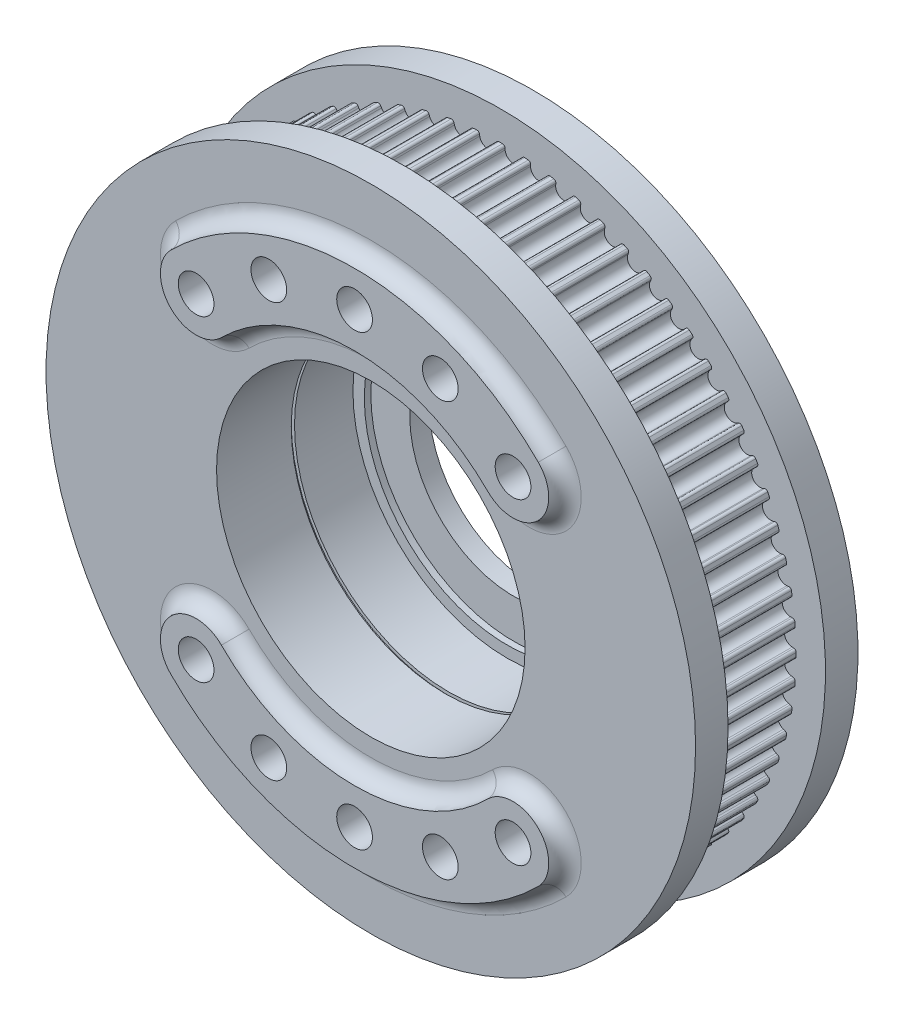
SolidWorks part; units mm, degrees
ref_plane "前视基准面" through (0, 0, 0) normal (0, 0, 1) x (1, 0, 0)
ref_plane "上视基准面" through (0, 0, 0) normal (0, 1, 0) x (1, 0, 0)
ref_plane "右视基准面" through (0, 0, 0) normal (1, 0, 0) x (0, 0, -1)
sketch "Sketch2" plane through (0, 0, 0) normal (0, 0, 1) x (1, 0, 0)
  circle A0 centre (0, 0) radius 90.99
  dimension "D1" = 181.98
extrude "Extrude1" add sketch "Sketch2" along normal mid plane 30
sketch "Sketch1" plane through (0, 0, 0) normal (0, 0, 1) x (1, 0, 0)
  line L0 (0, 0) -> (0, 91.675) construction
  line L1 (0, 0) -> (-3.9988, 91.5877) construction
  line L2 (-1.3223, 90.2696) -> (-1.3645, 89.7327)
  line L3 (-6.5503, 90.0413) -> (-6.4614, 89.5101)
  circle A0 centre (0, 0) radius 91.675 construction
  arc A1 (-0.5494, 90.9883) -> (-7.3828, 90.69) centre (0, 0) ccw
  arc A2 (-6.4614, 89.5101) -> (-1.3645, 89.7327) centre (-3.9266, 89.9343) ccw
  arc A3 (-0.5494, 90.9883) -> (-1.3223, 90.2696) centre (-0.5447, 90.2084) ccw
  arc A4 (-7.3828, 90.69) -> (-6.5503, 90.0413) centre (-7.3196, 89.9126) cw
  point P4 (91.5877, 3.9988)
  point P5 (90.8907, 11.966)
  point P6 (89.5019, 19.8421)
  point P7 (87.432, 27.5672)
  point P8 (84.6967, 35.0825)
  point P9 (81.3167, 42.3308)
  point P10 (77.3179, 49.2569)
  point P11 (72.7307, 55.8082)
  point P12 (67.5899, 61.9347)
  point P13 (61.9347, 67.5899)
  point P14 (55.8082, 72.7307)
  point P15 (49.2569, 77.3179)
  point P16 (42.3308, 81.3167)
  point P17 (35.0825, 84.6967)
  point P18 (27.5672, 87.432)
  point P19 (19.8421, 89.5019)
  point P20 (11.966, 90.8907)
  point P21 (3.9988, 91.5877)
  point P22 (-3.9988, 91.5877)
  point P23 (-11.966, 90.8907)
  point P24 (-19.8421, 89.5019)
  point P25 (-27.5672, 87.432)
  point P26 (-35.0825, 84.6967)
  point P27 (-42.3308, 81.3167)
  point P28 (-49.2569, 77.3179)
  point P29 (-55.8082, 72.7307)
  point P30 (-61.9347, 67.5899)
  point P31 (-67.5899, 61.9347)
  point P32 (-72.7307, 55.8082)
  point P33 (-77.3179, 49.2569)
  point P34 (-81.3167, 42.3308)
  point P35 (-84.6967, 35.0825)
  point P36 (-87.432, 27.5672)
  point P37 (-89.5019, 19.8421)
  point P38 (-90.8907, 11.966)
  point P39 (-91.5877, 3.9988)
  point P40 (-91.5877, -3.9988)
  point P41 (-90.8907, -11.966)
  point P42 (-89.5019, -19.8421)
  point P43 (-87.432, -27.5672)
  point P44 (-84.6967, -35.0825)
  point P45 (-81.3167, -42.3308)
  point P46 (-77.3179, -49.2569)
  point P47 (-72.7307, -55.8082)
  point P48 (-67.5899, -61.9347)
  point P49 (-61.9347, -67.5899)
  point P50 (-55.8082, -72.7307)
  point P51 (-49.2569, -77.3179)
  point P52 (-42.3308, -81.3167)
  point P53 (-35.0825, -84.6967)
  point P54 (-27.5672, -87.432)
  point P55 (-19.8421, -89.5019)
  point P56 (-11.966, -90.8907)
  point P57 (-3.9988, -91.5877)
  point P58 (3.9988, -91.5877)
  point P59 (11.966, -90.8907)
  point P60 (19.8421, -89.5019)
  point P61 (27.5672, -87.432)
  point P62 (35.0825, -84.6967)
  point P63 (42.3308, -81.3167)
  point P64 (49.2569, -77.3179)
  point P65 (55.8082, -72.7307)
  point P66 (61.9347, -67.5899)
  point P67 (67.5899, -61.9347)
  point P68 (72.7307, -55.8082)
  point P69 (77.3179, -49.2569)
  point P70 (81.3167, -42.3308)
  point P71 (84.6967, -35.0825)
  point P72 (87.432, -27.5672)
  point P73 (89.5019, -19.8421)
  point P74 (90.8907, -11.966)
  point P75 (91.5877, -3.9988)
  dimension "D1" = 183.35
  dimension "D2" = 181.98
  dimension "D3" = 5.14
  dimension "D4" = 3.54
  dimension "D5" = 1.56
  dimension "D6" = 7
extrude "Extrude2" cut sketch "Sketch1" along normal mid plane 30
pattern_circular "CirPattern1" count 72 over 360 about axis through (0, 0, 0) along (0, 0, 1) of "Extrude2"
sketch "Sketch3" plane through (0, 0, 15) normal (0, 0, 1) x (1, 0, 0)
  circle A0 centre (0, 0) radius 100
  dimension "D1" = 200
extrude "Extrude3" add sketch "Sketch3" along normal blind 10
sketch "Sketch4" plane through (0, 0, -15) normal (0, 0, -1) x (-1, 0, 0)
  circle A0 centre (0, 0) radius 100
  circle A1 centre (0, 0) radius 100 construction
extrude "Extrude4" add sketch "Sketch4" along normal blind 10
sketch "Sketch6" plane through (0, 0, -25) normal (0, 0, -1) x (-1, 0, 0)
  line L0 (0, 0) -> (0, 100) construction
  line L1 (-48.7904, 48.7904) -> (0, 0) construction
  line L2 (0, 0) -> (100, 0) construction
  arc A0 (48.7904, 48.7904) -> (-48.7904, 48.7904) centre (0, 0) ccw construction
  arc A1 (56.5685, 56.5685) -> (-56.5685, 56.5685) centre (0, 0) ccw
  arc A2 (41.0122, 41.0122) -> (-41.0122, 41.0122) centre (0, 0) ccw
  arc A3 (41.0122, 41.0122) -> (56.5685, 56.5685) centre (48.7904, 48.7904) ccw
  arc A4 (-56.5685, 56.5685) -> (-41.0122, 41.0122) centre (-48.7904, 48.7904) ccw
  circle A5 centre (0, 0) radius 100 construction
  arc A6 (48.7904, -48.7904) -> (-48.7904, -48.7904) centre (0, 0) cw construction
  arc A7 (56.5685, -56.5685) -> (-56.5685, -56.5685) centre (0, 0) cw
  arc A8 (41.0122, -41.0122) -> (-41.0122, -41.0122) centre (0, 0) cw
  arc A9 (41.0122, -41.0122) -> (56.5685, -56.5685) centre (48.7904, -48.7904) cw
  arc A10 (-56.5685, -56.5685) -> (-41.0122, -41.0122) centre (-48.7904, -48.7904) cw
  point P4 (0, 69)
  point P15 (26.4052, 63.7477)
  point P16 (0, 69)
  point P17 (-26.4052, 63.7477)
  point P20 (0, -69)
  point P25 (26.4052, -63.7477)
  point P26 (0, -69)
  point P27 (-26.4052, -63.7477)
  dimension "D1" = 69
  dimension "D2" = 11
  dimension "D3" = 45
extrude "Extrude6" cut sketch "Sketch6" against normal blind 18
hole_wizard "Ø11.0 (11) Diameter Hole1" positions "Sketch8" profile "Sketch9" hole size "Ø11.0" standard "GB" end condition through all
sketch "Sketch8" plane through (0, 0, -7) normal (0, 0, -1) x (-1, 0, 0)
  point P0 (-48.7904, 48.7904)
  point P3 (48.7904, 48.7904)
  point P6 (-26.4052, 63.7477)
  point P9 (0, 69)
  point P12 (26.4052, 63.7477)
  point P15 (-48.7904, -48.7904)
  point P18 (-26.4052, -63.7477)
  point P21 (0, -69)
  point P24 (26.4052, -63.7477)
  point P27 (48.7904, -48.7904)
sketch "Sketch9" plane through (48.7904, 48.7904, -7) normal (1, 0, 0) x (0, 1, 0)
  line L0 (0, 0) -> (0, 32)
  line L1 (0, 32) -> (5.5, 32)
  line L2 (5.5, 32) -> (5.5, 0)
  line L5 (5.5, 0) -> (0, 0)
  line L11 (0, -6.35) -> (0, 107.95) construction
  dimension "通孔孔直径" = 11
  dimension "通孔孔深度" = 32
sketch "Sketch11" plane through (0, 0, 25) normal (0, 0, 1) x (1, 0, 0)
  arc A0 (-41.0122, -41.0122) -> (-56.5685, -56.5685) centre (-48.7904, -48.7904) ccw construction
  arc A1 (-41.0122, -41.0122) -> (41.0122, -41.0122) centre (0, 0) ccw construction
  arc A2 (56.5685, -56.5685) -> (41.0122, -41.0122) centre (48.7904, -48.7904) ccw construction
  arc A3 (-56.5685, -56.5685) -> (56.5685, -56.5685) centre (0, 0) ccw construction
  arc A4 (-56.5685, 56.5685) -> (-41.0122, 41.0122) centre (-48.7904, 48.7904) ccw construction
  arc A5 (56.5685, 56.5685) -> (-56.5685, 56.5685) centre (0, 0) ccw construction
  arc A6 (41.0122, 41.0122) -> (56.5685, 56.5685) centre (48.7904, 48.7904) ccw construction
  arc A7 (41.0122, 41.0122) -> (-41.0122, 41.0122) centre (0, 0) ccw construction
  arc A8 (-41.0122, -41.0122) -> (-56.5685, -56.5685) centre (-48.7904, -48.7904) ccw
  arc A9 (-41.0122, -41.0122) -> (41.0122, -41.0122) centre (0, 0) ccw
  arc A10 (56.5685, -56.5685) -> (41.0122, -41.0122) centre (48.7904, -48.7904) ccw
  arc A11 (-56.5685, -56.5685) -> (56.5685, -56.5685) centre (0, 0) ccw
  arc A12 (-56.5685, 56.5685) -> (-41.0122, 41.0122) centre (-48.7904, 48.7904) ccw
  arc A13 (56.5685, 56.5685) -> (-56.5685, 56.5685) centre (0, 0) ccw
  arc A14 (41.0122, 41.0122) -> (56.5685, 56.5685) centre (48.7904, 48.7904) ccw
  arc A15 (41.0122, 41.0122) -> (-41.0122, 41.0122) centre (0, 0) ccw
  circle A17 centre (48.7904, 48.7904) radius 5.5
  circle A18 centre (48.7904, 48.7904) radius 5.5
  circle A19 centre (26.4052, 63.7477) radius 5.5
  circle A20 centre (26.4052, 63.7477) radius 5.5
  circle A21 centre (0, 69) radius 5.5
  circle A22 centre (0, 69) radius 5.5
  circle A23 centre (-26.4052, 63.7477) radius 5.5
  circle A24 centre (-26.4052, 63.7477) radius 5.5
  circle A25 centre (-48.7904, 48.7904) radius 5.5
  circle A26 centre (-48.7904, 48.7904) radius 5.5
  circle A27 centre (-48.7904, -48.7904) radius 5.5
  circle A28 centre (-48.7904, -48.7904) radius 5.5
  circle A29 centre (48.7904, -48.7904) radius 5.5
  circle A30 centre (48.7904, -48.7904) radius 5.5
  circle A31 centre (-26.4052, -63.7477) radius 5.5
  circle A32 centre (-26.4052, -63.7477) radius 5.5
  circle A33 centre (0, -69) radius 5.5
  circle A34 centre (0, -69) radius 5.5
  circle A35 centre (26.4052, -63.7477) radius 5.5
  circle A36 centre (26.4052, -63.7477) radius 5.5
  dimension "D1" = 0
  dimension "D2" = 0
  dimension "D3" = 0
  dimension "D4" = 0
  dimension "D5" = 0
  dimension "D6" = 0
  dimension "D7" = 0
  dimension "D8" = 0
  dimension "D9" = 0
  dimension "D10" = 0
extrude "Extrude8" add sketch "Sketch11" along normal blind 5
fillet "Fillet1" radius 1.5 8 edges at (56.5685, -41.0122, -7) (0, -58, -7) (-56.5685, -41.0122, -7) (0, -80, -7) (0, 58, -7) (56.5685, 41.0122, -7) (-56.5685, 41.0122, -7) (0, 80, -7)
fillet "Fillet2" radius 5 8 edges at (0, 58, 25) (56.5685, 41.0122, 25) (-56.5685, 41.0122, 25) (0, 80, 25) (0, -80, 25) (56.5685, -41.0122, 25) (-56.5685, -41.0122, 25) (0, -58, 25)
sketch "Sketch12" plane through (0, 0, 0) normal (0, 1, 0) x (1, 0, 0)
  line L0 (0, 25) -> (0, -30) construction
  line L1 (0, 25) -> (0, -30)
  line L17 (56.5685, 25) -> (-56.5685, 25) construction
  line L18 (-56.5685, -30) -> (56.5685, -30) construction
  line L19 (0, 25) -> (32, 25)
  line L20 (32, 25) -> (32, 19)
  line L21 (32, 19) -> (44, 19)
  line L22 (44, 19) -> (44, 17)
  line L23 (44, 17) -> (47.5, 17)
  line L24 (47.5, 17) -> (47.5, -1)
  line L25 (47.5, -1) -> (48.5, -1)
  line L26 (48.5, -1) -> (48.5, -2)
  line L27 (48.5, -2) -> (47.5, -2)
  line L28 (47.5, -2) -> (47.5, -30)
  line L29 (47.5, -30) -> (0, -30)
  dimension "D1" = 95
  dimension "D2" = 97
  dimension "D3" = 64
  dimension "D4" = 88
  dimension "D5" = 1
  dimension "D6" = 18
  dimension "D7" = 2
  dimension "D8" = 6
revolve "Cut-Revolve1" cut sketch "Sketch12" angle 360 about L0
